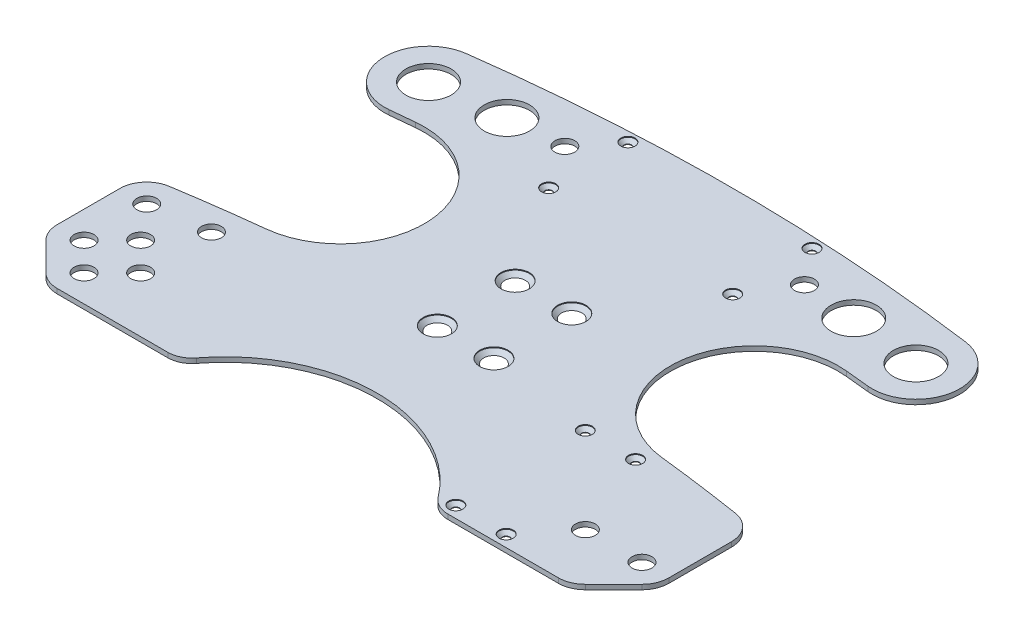
SolidWorks part; units mm, degrees
ref_plane "Front Plane" through (0, 0, 0) normal (0, 0, 1) x (1, 0, 0)
ref_plane "Top Plane" through (0, 0, 0) normal (0, 1, 0) x (1, 0, 0)
ref_plane "Right Plane" through (0, 0, 0) normal (1, 0, 0) x (0, 0, -1)
sketch "Sketch1" plane through (0, 0, 0) normal (0, 1, 0) x (1, 0, 0)
  line L1 (-120, -95) -> (120, -95)
  line L2 (-120, -95) -> (-120, 95)
  line L3 (-120, 95) -> (120, 95)
  line L4 (120, -95) -> (120, 95)
  line L5 (-120, -95) -> (120, 95) construction
  line L6 (-120, 95) -> (120, -95) construction
  line L7 (-10, 13.75) -> (10, 13.75)
  line L8 (-10, 13.75) -> (-10, -13.75)
  line L9 (-10, -13.75) -> (10, -13.75)
  line L10 (10, 13.75) -> (10, -13.75)
  line L11 (-10, 13.75) -> (10, -13.75) construction
  line L12 (-10, -13.75) -> (10, 13.75) construction
  circle A0 centre (0, 0) radius 95
  circle A1 centre (-10, 13.75) radius 2.5
  circle A2 centre (10, 13.75) radius 2.5
  circle A3 centre (10, -13.75) radius 2.5
  circle A4 centre (-10, -13.75) radius 2.5
  circle A5 centre (0, 0) radius 120
  dimension "D3" = 5
  dimension "D1" = 240
  dimension "D2" = 190
  dimension "D4" = 27.5
  dimension "D5" = 20
extrude "Boss-Extrude1" add sketch "Sketch1" along normal blind 1.69 contours A0 A4 L8 A1 L7 A2 L10 A3 L9 | A4 L9 A3 L10 A2 L7 A1 L8 | L3 A5 L1 A0 | L1 A5 L3 A0 region at (-105.6812, 0, 51.9346) region at (68.7642, 0, 68.7642) region at (-92.313, 0, 0) region at (0, 0, 0)
sketch "Sketch2" plane through (0, 1.69, 0) normal (0, 1, 0) x (1, 0, 0)
  line L0 (-81.1673, -40) -> (21.9115, -40) construction
  line L1 (-127.3056, -60) -> (138.909, -60) construction
  line L2 (-88.5406, 28.139) -> (-88.5406, -89.0376) construction
  line L3 (-88.5406, -40) -> (-88.5406, -60) construction
  line L4 (0, 21.6044) -> (0, -21.4213) construction
  line L5 (88.5406, 33.139) -> (88.5406, -84.0376) construction
  line L6 (-151.9803, -25) -> (55.006, -25) construction
  line L7 (-48.8837, 35) -> (62.426, 35) construction
  circle A0 centre (0, 0) radius 35
  circle A1 centre (0, 35) radius 2.5
  circle A2 centre (30.3109, 17.5) radius 2.5
  circle A3 centre (30.3109, -17.5) radius 2.5
  circle A4 centre (0, -35) radius 2.5
  circle A5 centre (-30.3109, -17.5) radius 2.5
  circle A6 centre (-30.3109, 17.5) radius 2.5
  circle A7 centre (-88.5406, -40) radius 3.5
  circle A8 centre (-88.5406, -50) radius 10
  circle A9 centre (-78.5406, -50) radius 3.5
  circle A10 centre (-88.5406, -60) radius 3.5
  circle A11 centre (-98.5406, -50) radius 3.5
  circle A12 centre (78.5406, -50) radius 3.5
  circle A13 centre (98.5406, -50) radius 3.5
  circle A14 centre (-98.5406, -27.8625) radius 3.5
  circle A15 centre (-78.5406, -25) radius 3.5
  circle A16 centre (0, 0) radius 45
  circle A17 centre (0, -580) radius 625
  circle A18 centre (0, -580) radius 645
  circle A19 centre (-86.0945, 59.2282) radius 8
  circle A20 centre (-61.2596, 62.0843) radius 8
  circle A21 centre (-86.0945, 59.2282) radius 15.5
  arc A22 (-73.3144, 95) -> (-73.3144, -95) centre (0, 0) ccw construction
  circle A23 centre (-61.2596, 62.0843) radius 9.5
  circle A24 centre (-86.0945, 59.2282) radius 9.5
  circle A25 centre (61.2596, 62.0843) radius 8
  circle A26 centre (86.0945, 59.2282) radius 8
  circle A27 centre (-42.3209, 63.6101) radius 3.5
  circle A28 centre (0, 0) radius 70
  circle A29 centre (42.3209, 63.6101) radius 3.5
  circle A30 centre (-98.5406, -50) radius 9.5
  circle A31 centre (42.3209, 63.6101) radius 9.5
  circle A32 centre (61.2596, 62.0843) radius 9.5
  circle A33 centre (0, -645.0455) radius 625
  point P17 (0, 0)
  point P21 (-88.5406, -50)
  point P37 (-88.5406, -50)
  point P56 (0, 65)
  point P57 (0, 45)
  point P68 (-76.6704, 60.4269)
  point P69 (-70.7097, 61.1124)
  dimension "D1" = 70
  dimension "D2" = 5
  dimension "D4" = 7
  dimension "D9" = 90
  dimension "D10" = 1250
  dimension "D11" = 20
  dimension "D12" = 16
  dimension "D14" = 6
  dimension "D13" = 19
  dimension "D17" = 140
  dimension "D18" = 6
  dimension "D5" = 20
  dimension "D6" = 40
  dimension "D8" = 15
  dimension "D15" = 6
  dimension "D3" = 6
  dimension "D7" = 4
extrude "Cut-Extrude1" cut sketch "Sketch2" against normal up to next contours A7 | A9 | A10 | A11 | A12 | A13 | A14 | A15 | A19 | A20 | A25 | A26 | A27 | A29
sketch "Sketch3" plane through (0, 1.69, 0) normal (0, 1, 0) x (1, 0, 0)
  line L1 (-84.5506, 43.8053) -> (-40.7771, 48.1872)
  line L2 (0, 100.6986) -> (0, -98.8678) construction
  line L3 (-10.3445, 0) -> (20.4144, 0) construction
  line L5 (84.5506, 43.8053) -> (40.7771, 48.1872)
  line L6 (-42.3209, 63.6101) -> (0, 0) construction
  line L7 (-36.306, 26.5871) -> (-55.2257, 55.0243)
  line L8 (-10.4964, 43.7587) -> (-29.4161, 72.1959)
  line L9 (10.4964, 43.7587) -> (29.4161, 72.1959)
  line L10 (36.306, 26.5871) -> (55.2257, 55.0243)
  line L11 (-108.0406, -50) -> (-108.0406, -27.8625)
  line L13 (-73.3144, -95) -> (73.3144, -95)
  line L14 (73.3144, 95) -> (-73.3144, 95)
  line L15 (-73.3144, -95) -> (73.3144, -95)
  line L16 (73.3144, 95) -> (-73.3144, 95)
  line L17 (-69.0406, -25) -> (-69.0406, -50)
  line L18 (-71.8231, -56.7175) -> (-81.8231, -66.7175)
  line L19 (-105.2581, -56.7175) -> (-95.2581, -66.7175)
  line L20 (-42.3209, 79.1101) -> (42.3209, 79.1101)
  line L21 (-78.5406, -15.5) -> (-42.2463, -15.5)
  line L22 (0, -45) -> (111.243, -45) construction
  line L23 (-88.5406, -69.5) -> (88.5406, -69.5)
  line L24 (69.0406, -15.5) -> (45.0406, -15.5)
  line L25 (78.5406, -15.5) -> (42.2463, -15.5)
  line L27 (108.0406, -50) -> (108.0406, -27.8625)
  line L28 (105.2581, -56.7175) -> (95.2581, -66.7175)
  line L29 (69.0406, -15.5) -> (69.0406, -69.5)
  line L30 (69.0406, -69.5) -> (45.0406, -69.5)
  line L31 (45.0406, -15.5) -> (45.0406, -69.5)
  line L32 (57.0406, -15.5) -> (57.0406, -69.5) construction
  line L33 (45.0406, -42.5) -> (69.0406, -42.5) construction
  circle A0 centre (-86.0945, 59.2282) radius 15.5
  arc A1 (-73.3144, 95) -> (-73.3144, -95) centre (0, 0) ccw construction
  circle A2 centre (-42.3209, 63.6101) radius 15.5
  circle A3 centre (86.0945, 59.2282) radius 15.5
  circle A4 centre (42.3209, 63.6101) radius 15.5
  circle A5 centre (0, 0) radius 45
  circle A6 centre (-98.5406, -27.8625) radius 9.5
  circle A7 centre (-98.5406, -27.8625) radius 3.5 construction
  arc A8 (-73.3144, 95) -> (-73.3144, -95) centre (0, 0) ccw
  arc A9 (73.3144, -95) -> (73.3144, 95) centre (0, 0) ccw
  arc A10 (-73.3144, 95) -> (-73.3144, -95) centre (0, 0) ccw
  arc A11 (73.3144, -95) -> (73.3144, 95) centre (0, 0) ccw
  circle A12 centre (-78.5406, -25) radius 9.5
  circle A13 centre (-88.5406, -60) radius 9.5
  circle A14 centre (-98.5406, -50) radius 9.5
  circle A15 centre (-78.5406, -50) radius 9.5
  circle A17 centre (98.5406, -50) radius 9.5
  circle A18 centre (78.5406, -50) radius 9.5
  arc A19 (73.3144, -95) -> (73.3144, 95) centre (0, 0) ccw construction
  arc A20 (-45.0406, -69.5) -> (45.0406, -69.5) centre (0, -98.6511) cw
  circle A21 centre (98.5406, -27.8625) radius 9.5
  circle A22 centre (98.5406, -50) radius 9.5
  circle A23 centre (88.5406, -60) radius 9.5
  circle A24 centre (-73.1485, 15.1063) radius 29.692
  circle A25 centre (73.1485, 15.1063) radius 29.692
  circle A26 centre (48.1506, -19.64) radius 1.3
  circle A27 centre (65.9306, -19.64) radius 1.3
  circle A28 centre (65.9306, -65.36) radius 1.3
  circle A29 centre (48.1506, -65.36) radius 1.3
  circle A30 centre (0, -580) radius 645
  circle A31 centre (0, -580) radius 660.5
  circle A32 centre (0, -645.0455) radius 634.5
  arc M45 (-73.3144, 95) -> (-73.3144, -95) centre (0, 0) ccw
  line M46 (-73.3144, -95) -> (73.3144, -95)
  arc M47 (73.3144, -95) -> (73.3144, 95) centre (0, 0) ccw
  line M48 (73.3144, 95) -> (-73.3144, 95)
  dimension "D1" = 90
  dimension "D3" = 6
  dimension "D5" = 2.6
  dimension "D4" = 24
  dimension "D6" = 17.78
  dimension "D7" = 45.72
  dimension "D2" = 0
extrude "Cut-Extrude2" cut sketch "Sketch3" against normal up to next contours A24 L1 A0 A14 L11 A6 L21 M45 | A24 | L28 A23 L23 A13 L19 A14 A10 A17 M46 M47 | A20 L23 | L5 A25 L24 L25 A21 L27 A17 A11 A3 | A25 | A30 A0 M45 | A31 A11 M48 M45 | A0 A31 A10 | A31 A3 M47 | A30 A3 M47 | A6 A32 A14 L11 M45 | A11 A32 A21 L27 A17 | A26 | A27 | A28 | A29 region at (-105.8887, 1.69, -12.959) region at (-73.1485, 1.69, -15.1063) region at (-102.839, 1.69, -59.5932) region at (-94.2652, 1.69, -72.7135) region at (0, 1.69, -86.2332) region at (-111.2756, 1.69, 31.2797) region at (0, 1.69, 81.3426) region at (0, 1.69, 59.4787) region at (73.1485, 1.69, -15.1063) region at (105.8887, 1.69, -12.959) region at (111.2756, 1.69, 31.2797) region at (94.2652, 1.69, -72.7135) region at (102.839, 1.69, -59.5932)
hole_wizard "CSK for M5 Flat Head Machine Screw1" positions "Sketch4" profile "Sketch5" countersink size "M5" standard "ANSI Metric"
sketch "Sketch4" plane through (0, 1.69, 0) normal (0, 1, 0) x (1, 0, 0)
  point P0 (-10, 13.75)
  point P3 (10, 13.75)
  point P6 (10, -13.75)
  point P9 (-10, -13.75)
sketch "Sketch5" plane through (-10, 1.69, -13.75) normal (1, 0, 0) x (0, 0, 1)
  line L0 (0, 0) -> (0, 6.5022)
  line L1 (0, 6.5022) -> (2.5, 5)
  line L2 (2.5, 5) -> (2.5, 2.8)
  line L3 (2.5, 2.8) -> (5, 0.3)
  line L4 (5, 0.3) -> (5, 0)
  line L6 (5, 0) -> (0, 0)
  line L7 (-2.5, 2.8) -> (-5, 0.3) construction
  line L10 (0, 6.5022) -> (-2.5, 5) construction
  line L11 (0, -6.35) -> (0, 107.95) construction
  dimension "Hole Dia." = 5
  dimension "Hole Depth" = 5
  dimension "C'Sink Dia." = 10
  dimension "C'Sink Angle" = 90
  dimension "Drill Angle" = 118
  dimension "Head Clearance" = 0.3
sketch "Sketch8" plane through (0, 0, 0) normal (0, -1, 0) x (1, 0, 0)
  line L0 (-69.2596, -62.0843) -> (69.2596, -62.0843) construction
  line L2 (-32.5, -48.0843) -> (32.5, -48.0843)
  line L3 (-32.5, -48.0843) -> (-32.5, -76.0843)
  line L4 (-32.5, -76.0843) -> (32.5, -76.0843)
  line L5 (32.5, -48.0843) -> (32.5, -76.0843)
  line L6 (-32.5, -48.0843) -> (32.5, -76.0843) construction
  line L7 (-32.5, -76.0843) -> (32.5, -48.0843) construction
  circle A0 centre (-61.2596, -62.0843) radius 8 construction
  circle A1 centre (61.2596, -62.0843) radius 8 construction
  circle A2 centre (-32.5, -48.0843) radius 1.3
  circle A3 centre (32.5, -48.0843) radius 1.3
  circle A4 centre (32.5, -76.0843) radius 1.3
  circle A5 centre (-32.5, -76.0843) radius 1.3
  circle A6 centre (48.1506, 19.64) radius 1.3 construction
  point P7 (0, -62.0843)
  dimension "D1" = 65
  dimension "D2" = 28
extrude "Cut-Extrude3" cut sketch "Sketch8" against normal up to next contours A2 | A3 | A4 | A5
hole_wizard "CSK for M2.5 Flat Head Machine Screw1" positions "Sketch6" profile "Sketch7" countersink size "M2.5" standard "ANSI Metric"
sketch "Sketch6" plane through (0, 1.69, 0) normal (0, 1, 0) x (1, 0, 0)
  point P0 (48.1506, -19.64)
  point P3 (65.9306, -19.64)
  point P6 (65.9306, -65.36)
  point P9 (48.1506, -65.36)
  point P27 (32.5, 76.0843)
  point P30 (32.5, 48.0843)
  point P33 (-32.5, 76.0843)
  point P36 (-32.5, 48.0843)
sketch "Sketch7" plane through (48.1506, 1.69, 19.64) normal (1, 0, 0) x (0, 0, 1)
  line L0 (0, 0) -> (0, 5.7511)
  line L1 (0, 5.7511) -> (1.25, 5)
  line L2 (1.25, 5) -> (1.25, 1.55)
  line L3 (1.25, 1.55) -> (2.5, 0.3)
  line L4 (2.5, 0.3) -> (2.5, 0)
  line L6 (2.5, 0) -> (0, 0)
  line L7 (-1.25, 1.55) -> (-2.5, 0.3) construction
  line L10 (0, 5.7511) -> (-1.25, 5) construction
  line L11 (0, -6.35) -> (0, 107.95) construction
  dimension "Hole Dia." = 2.5
  dimension "Hole Depth" = 5
  dimension "C'Sink Dia." = 5
  dimension "C'Sink Angle" = 90
  dimension "Drill Angle" = 118
  dimension "Head Clearance" = 0.3
fillet "Fillet1" radius 8.5 2 edges at (45.0406, 0.845, 69.5) (-45.0406, 0.845, 69.5)
